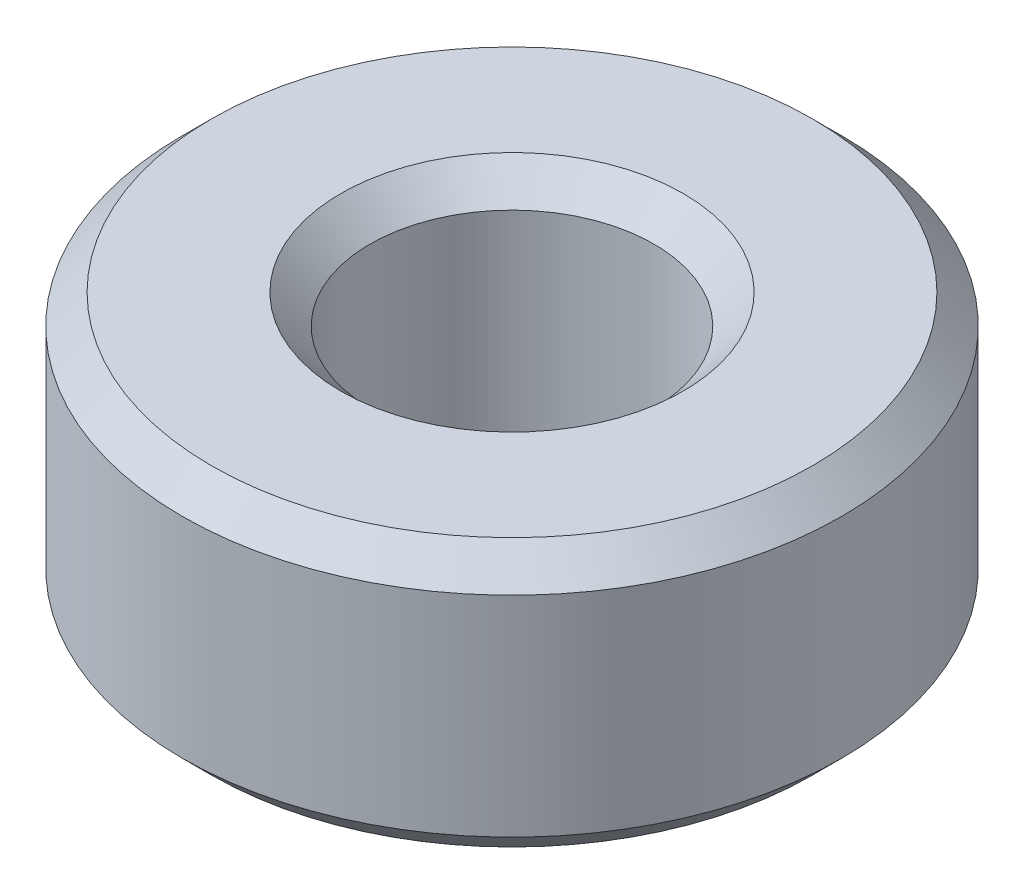
SolidWorks part; units mm, degrees
ref_plane "Front Plane" through (0, 0, 0) normal (0, 0, 1) x (1, 0, 0)
ref_plane "Top Plane" through (0, 0, 0) normal (0, 1, 0) x (1, 0, 0)
ref_plane "Right Plane" through (0, 0, 0) normal (1, 0, 0) x (0, 0, -1)
sketch "Sketch1" plane through (0, 0, 0) normal (0, 1, 0) x (1, 0, 0)
  circle A0 centre (0, 0) radius 40
  dimension "SLEEVE_OD" = 80
extrude "Boss-Extrude1" add sketch "Sketch1" along normal blind 32.5057
sketch "Sketch2" plane through (0, 0, 0) normal (0, 1, 0) x (1, 0, 0)
  circle A0 centre (0, 0) radius 17.2287
  dimension "BORE_D" = 34.4575
extrude "Cut-Extrude1" cut sketch "Sketch2" along normal through all
chamfer "Chamfer1" distance 3.5449 angle 45 4 edges at (0, 32.5057, 17.2287) (0, 0, 17.2287) (0, 0, 40) (0, 32.5057, 40)
